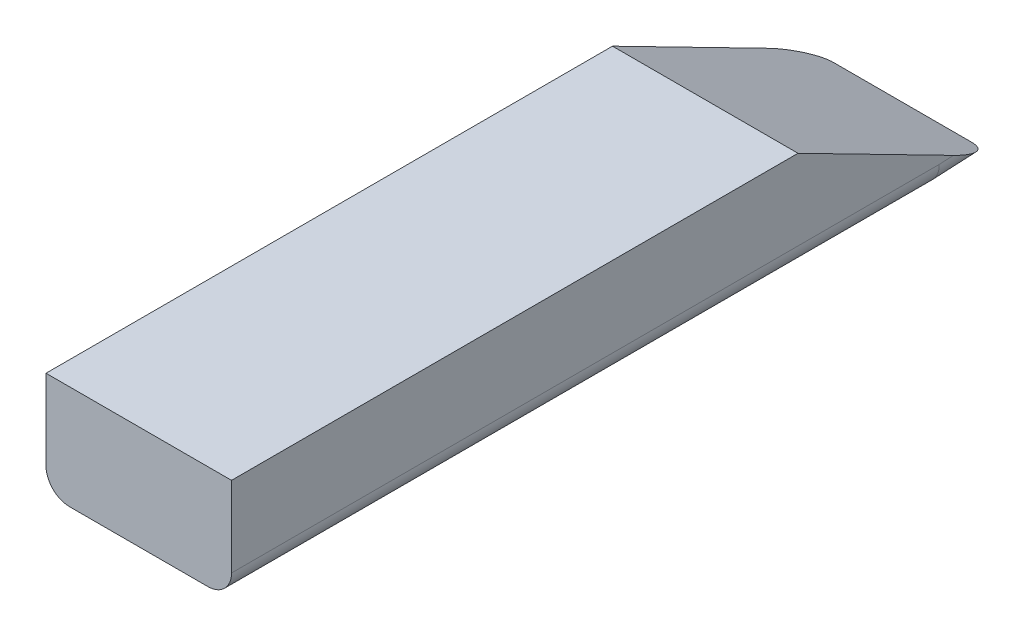
SolidWorks part; units mm, degrees
ref_plane "Front Plane" through (0, 0, 0) normal (0, 0, 1) x (1, 0, 0)
ref_plane "Top Plane" through (0, 0, 0) normal (0, 1, 0) x (1, 0, 0)
ref_plane "Right Plane" through (0, 0, 0) normal (1, 0, 0) x (0, 0, -1)
sketch "Sketch1" plane through (0, 0, 0) normal (1, 0, 0) x (0, 0, -1)
  line L0 (0, 0) -> (0, 55.88)
  line L1 (0, 55.88) -> (304.8, 55.88)
  line L2 (304.8, 55.88) -> (411.0358, 1.5164)
  line L3 (411.0358, 1.5164) -> (381.1016, 0)
  line L4 (381.1016, 0) -> (0, 0)
  dimension "D1" = 30
  dimension "D2" = 55.88
  dimension "D3" = 304.8
  dimension "D4" = 381.1016
  dimension "D5" = 177.1
extrude "Boss-Extrude1" add sketch "Sketch1" along normal mid plane 99.822
fillet "Fillet1" radius 12.7 4 edges at (49.911, 0.7582, -396.0687) (-49.911, 0.7582, -396.0687) (-49.911, 0, -190.5508) (49.911, 0, -190.5508)
